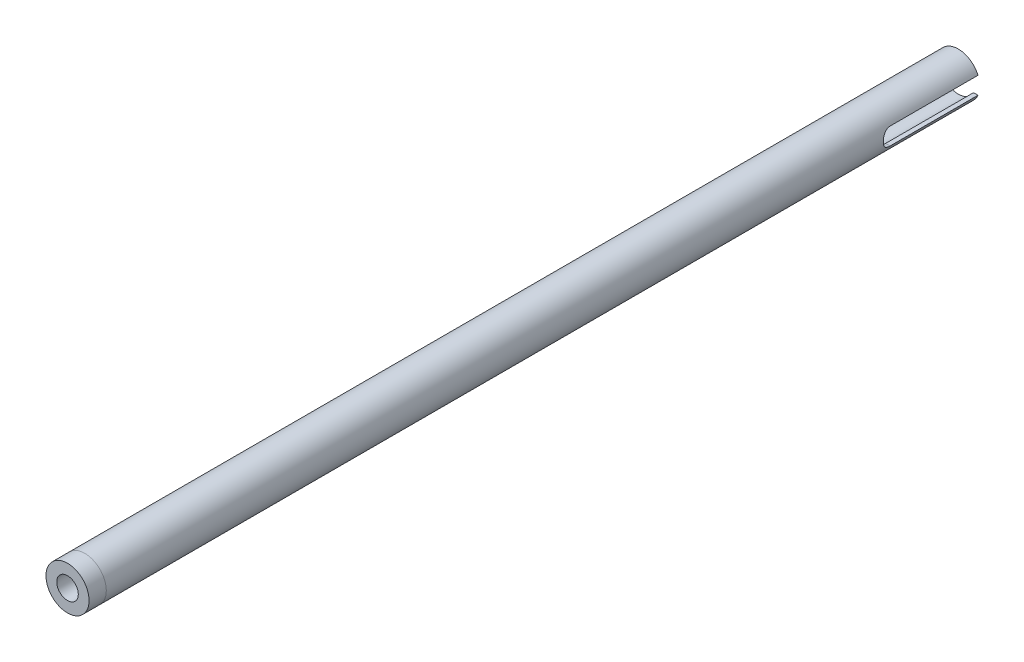
SolidWorks part; units mm, degrees
material "AISI 4130 Steel, normalized at 870C"
ref_plane "Front Plane" through (0, 0, 0) normal (0, 0, 1) x (1, 0, 0)
ref_plane "Top Plane" through (0, 0, 0) normal (0, 1, 0) x (1, 0, 0)
ref_plane "Right Plane" through (0, 0, 0) normal (1, 0, 0) x (0, 0, -1)
sketch "Axis" plane through (0, 0, 0) normal (0, 1, 0) x (1, 0, 0)
  line L0 (0, 0) -> (0, 328.0702) construction
  line L1 (0, 0) -> (0, -28.575) construction
  line L2 (0, 328.0702) -> (-7.9375, 328.0702) construction
  line L3 (0, 356.4735) -> (-26.4371, 261.8721) construction
  dimension "D1" = 28.575
  dimension "D2" = 7.9375
sketch "Sketch1" plane through (0, 0, 0) normal (0, 0, 1) x (1, 0, 0)
  line L0 (-7.9375, 0) -> (7.9375, 0) construction
  line L1 (-7.2748, 3.175) -> (7.2748, 3.175)
  line L2 (-7.2748, -3.175) -> (7.2748, -3.175)
  circle A0 centre (0, 0) radius 7.9375
  circle A1 centre (0, 0) radius 6.4643
  circle A2 centre (0, 0) radius 3.9688
  dimension "D1" = 15.875
  dimension "D3" = 7.9375
  dimension "D2" = 1.4732
  dimension "D4" = 6.35
extrude "Threaded insert 1-1" add sketch "Sketch1" against normal blind 6.35 contours A2 L1 A1 | A1 L1 A0 | A2 L0 A1 L1 | A1 L0 A0 L1 | L0 A1 L2 A0 | L0 A2 L2 A1 | A2 L2 A1 | A1 L2 A0 | L0 A1 L2 A2 | L0 A0 L2 A1 | A0 L0 A1 L1 | A1 L0 A2 L1 region at (4.8156, 1.6537, 0) region at (4.8156, -1.6537, 0) region at (6.9501, 1.6161, 0) region at (6.9501, -1.6161, 0) region at (-4.8156, -1.6537, 0) region at (-4.8156, 1.6537, 0) region at (0, 4.6361, 0) region at (0, -4.6361, 0) region at (0, 6.6174, 0) region at (6.4528, -3.3281, 0) region at (-6.9501, -1.6161, 0) region at (-6.9501, 1.6161, 0)
extrude "Threaded insert 1-2" add sketch "Sketch1<3>" against normal blind 9.525 from surface contours A2 L1 A1 | A2 L0 A1 L1 | L0 A2 L2 A1 | A2 L2 A1 | L0 A1 L2 A2 | A1 L0 A2 L1 region at (4.8156, 1.6537, 0) region at (4.8156, -1.6537, 0) region at (-4.8156, -1.6537, 0) region at (-4.8156, 1.6537, 0) region at (0, 4.6361, 0) region at (0, -4.6361, 0) starting at face at (7.9375, 0, -6.35)
sketch "Sketch1<3>" plane through (0, 0, 0) normal (0, 0, 1) x (1, 0, 0) same geometry as "Sketch1"
extrude "A-arm tube" add sketch "Sketch1<4>" against normal up to vertex (328.0702 mm away) from surface separate body contours A1 L1 A0 | A1 L0 A0 L1 | L0 A1 L2 A0 | A1 L2 A0 | L0 A0 L2 A1 | A0 L0 A1 L1 region at (6.9501, 1.6161, 0) region at (6.9501, -1.6161, 0) region at (0, 6.6174, 0) region at (6.4528, -3.3281, 0) region at (-6.9501, -1.6161, 0) region at (-6.9501, 1.6161, 0) up to point (0, 0, -328.0702) starting at face at (6.4643, 0, -6.35)
sketch "Sketch1<4>" plane through (0, 0, 0) normal (0, 0, 1) x (1, 0, 0) same geometry as "Sketch1"
extrude "Apex slot" cut sketch "Sketch1<5>" along normal blind 35.56 from surface contours A0 L0 A1 L1 | L0 A0 L2 A1 | A1 L0 A0 L1 | L0 A1 L2 A0 region at (6.9501, 1.6161, 0) region at (6.9501, -1.6161, 0) region at (-6.9501, -1.6161, 0) region at (-6.9501, 1.6161, 0) starting at face at (6.4643, 0, -328.0702)
sketch "Sketch1<5>" plane through (0, 0, 0) normal (0, 0, 1) x (1, 0, 0) same geometry as "Sketch1"
fillet "Fillet1" radius 3.175 4 edges at (-6.4528, 3.175, -292.5102) (-6.4528, -3.175, -292.5102) (6.4528, -3.175, -292.5102) (6.4528, 3.175, -292.5102)
equation "\"tube diameter\"= 5 / 8"
equation "\"tube thickness\"= .058"
equation "\"apex thickness\"= .25"
equation "\"tube slot\"= 1.4"
equation "\"D1@Sketch1\"=\"tube diameter\""
equation "\"D2@Sketch1\"=\"tube thickness\""
equation "\"threaded insert hole\"= .3125"
equation "\"D3@Sketch1\"=\"threaded insert hole\""
equation "\"D4@Sketch1\"=\"apex thickness\""
equation "\"D1@Apex slot\" = \"tube slot\""
equation "\"D1@Fillet1\"=\"apex thickness\"/2"
